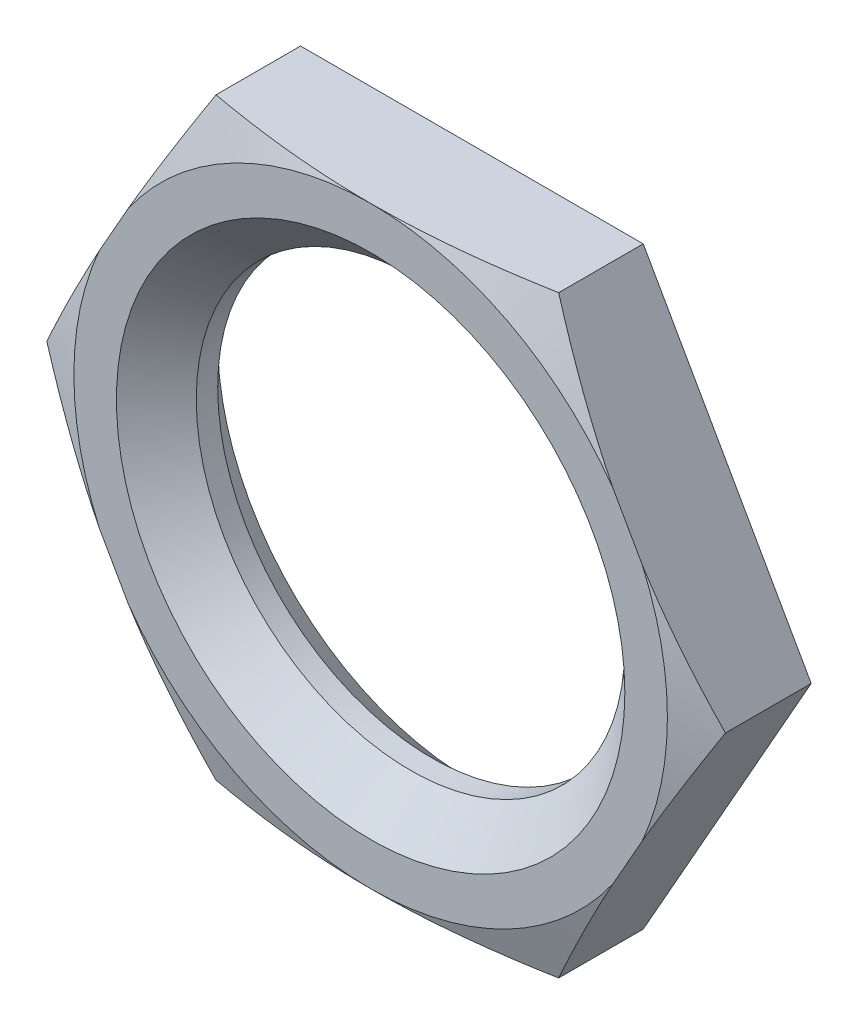
SolidWorks part; units mm, degrees
ref_plane "Front Plane" through (0, 0, 0) normal (0, 0, 1) x (1, 0, 0)
ref_plane "Top Plane" through (0, 0, 0) normal (0, 1, 0) x (1, 0, 0)
ref_plane "Right Plane" through (0, 0, 0) normal (1, 0, 0) x (0, 0, -1)
ref_plane "Plane1" through (0, 0, 0) normal (1, 0, 0) x (0, 0, -1)
sketch "Sketch1" plane through (0, 0, 0) normal (1, 0, 0) x (0, 0, -1)
  line L0 (-1.1938, 0) -> (-1.1938, 6.9977)
  line L1 (-1.1938, 6.9977) -> (-0.6844, 8.3972)
  line L2 (-0.6844, 8.3972) -> (1.1938, 8.3972)
  line L3 (1.1938, 8.3972) -> (1.1938, 0)
  line L4 (1.1938, 0) -> (-1.1938, 0)
  line L5 (1.1938, 0) -> (-1.1938, 0) construction
revolve "Revolve1" add sketch "Sketch1" angle 360 about L5 reverse direction yes
ref_plane "Plane2" through (0, 0, 0) normal (0, 0, 1) x (1, 0, 0)
sketch "Sketch2" plane through (0, 0, 0) normal (0, 0, 1) x (1, 0, 0)
  line L0 (-13.9954, 13.9954) -> (-13.9954, -13.9954)
  line L1 (-13.9954, -13.9954) -> (13.9954, -13.9954)
  line L2 (13.9954, -13.9954) -> (13.9954, 13.9954)
  line L3 (13.9954, 13.9954) -> (-13.9954, 13.9954)
  line L4 (-8.001, 0) -> (-4.0401, -6.9977)
  line L5 (-4.0401, -6.9977) -> (4.0401, -6.9977)
  line L6 (4.0401, -6.9977) -> (8.001, 0)
  line L7 (8.001, 0) -> (4.0401, 6.9977)
  line L8 (4.0401, 6.9977) -> (-4.0401, 6.9977)
  line L9 (-4.0401, 6.9977) -> (-8.001, 0)
extrude "Cut-Extrude1" cut sketch "Sketch2" against normal blind 2.3876 and the other way blind 2.3876
ref_plane "Plane3" through (0, 0, 0) normal (1, 0, 0) x (0, 0, -1)
sketch "Sketch3" plane through (0, 0, 0) normal (1, 0, 0) x (0, 0, -1)
  line L0 (-1.1938, 0) -> (-1.1938, 5.9944)
  line L1 (-1.1938, 5.9944) -> (-0.2524, 5.053)
  line L2 (-0.2524, 5.053) -> (0.2524, 5.053)
  line L3 (0.2524, 5.053) -> (1.1938, 5.9944)
  line L4 (1.1938, 5.9944) -> (1.1938, 0)
  line L5 (1.1938, 0) -> (-1.1938, 0)
  line L6 (1.1938, 0) -> (-1.1938, 0) construction
revolve "Cut-Revolve1" cut sketch "Sketch3" angle 360 about L6 reverse direction yes
